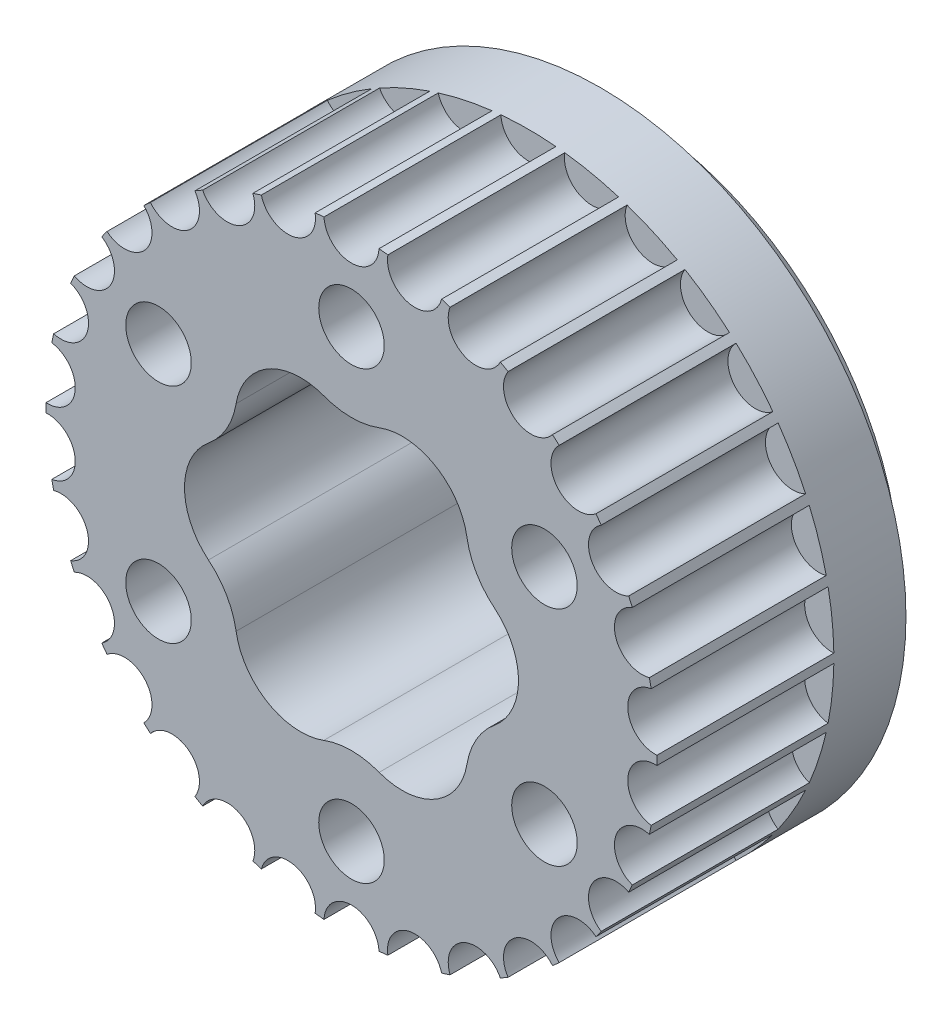
SolidWorks part; units mm, degrees
material "ABS"
ref_plane "Alzado" through (0, 0, 0) normal (0, 0, 1) x (1, 0, 0)
ref_plane "Planta" through (0, 0, 0) normal (0, 1, 0) x (1, 0, 0)
ref_plane "Vista lateral" through (0, 0, 0) normal (1, 0, 0) x (0, 0, -1)
sketch "Croquis1" plane through (0, 0, 0) normal (0, 0, 1) x (1, 0, 0)
  circle A0 centre (0, 0) radius 23.305
  dimension "Øexterior" = 46.61
extrude "Saliente-Extruir1" add sketch "Croquis1" along normal blind 21
sketch "Croquis2" plane through (0, 0, 21) normal (0, 0, 1) x (1, 0, 0)
  line L0 (0, 0) -> (0, 23.305) construction
  circle A0 centre (0, 0) radius 23.305 construction
  circle A1 centre (0, 23.305) radius 2.1
  dimension "ØdienteHTD5M" = 4.2
extrude "Cortar-Extruir1 diente" cut sketch "Croquis2" against normal through all
pattern_circular "MatrizC1 de dientes" count 30 over 360 about axis through (0, 0, 21) along (0, 0, -1) of "Cortar-Extruir1 diente"
sketch "Sketch1" plane through (0, 0, 0) normal (0, 0, -1) x (-1, 0, 0)
  circle A0 centre (0, 0) radius 23.305
  arc A1 (11.9455, 20.0107) -> (11.357, 20.3505) centre (0, 0) ccw construction
extrude "Boss-Extrude1" add sketch "Sketch1" against normal blind 7.5
sketch "Sketch2" plane through (0, 0, 0) normal (0, 0, -1) x (-1, 0, 0)
  circle A0 centre (0, 0) radius 22
  circle A1 centre (0, 0) radius 23.305
  circle A2 centre (0, 0) radius 23.305 construction
  dimension "D1" = 44
extrude "Cut-Extrude1" cut sketch "Sketch2" against normal blind 2
chamfer "Chamfer1" distance 2 angle 30 1 edges at (-22, 0, 0) first distance on face at (-22, 0, 2)
sketch "Sketch3" plane through (0, 0, 0) normal (0, 0, -1) x (-1, 0, 0)
  circle A0 centre (0, 0) radius 17 construction
  circle A1 centre (0, 17) radius 2.5
  dimension "D1" = 34
  dimension "D2" = 5
extrude "Cut-Extrude2" cut sketch "Sketch3" against normal through all
pattern_circular "CirPattern1" count 6 over 360 about axis through (0, 0, 2) along (0, 0, -1) of "Cut-Extrude2"
sketch "Sketch5" plane through (0, 0, 0) normal (0, 0, -1) x (-1, 0, 0)
  line L0 (0, 0) -> (0, 17) construction
  line L1 (-14.7224, 8.5) -> (0, 0) construction
  line L2 (0, 0) -> (-10.4226, 18.0526) construction
  line L3 (-9.5263, 5.5) -> (0, 0)
  line L4 (0, 0) -> (0, 11)
  arc A0 (-2.111, 11.3836) -> (-8.803, 7.52) centre (-3.8702, 6.7033) ccw
  arc A1 (-9.5263, 5.5) -> (-8.803, 7.52) centre (-14.7224, 8.5) ccw
  arc A2 (-2.111, 11.3836) -> (0, 11) centre (0, 17) ccw
  circle A3 centre (0, 0) radius 20.8453 construction
  dimension "D1" = 10
  dimension "D3" = 12
  dimension "D2" = 30
extrude "Cut-Extrude3" cut sketch "Sketch5" against normal through all
pattern_circular "CirPattern2" count 6 over 360 about axis through (0, 0, 2) along (0, 0, -1) of "Cut-Extrude3"
